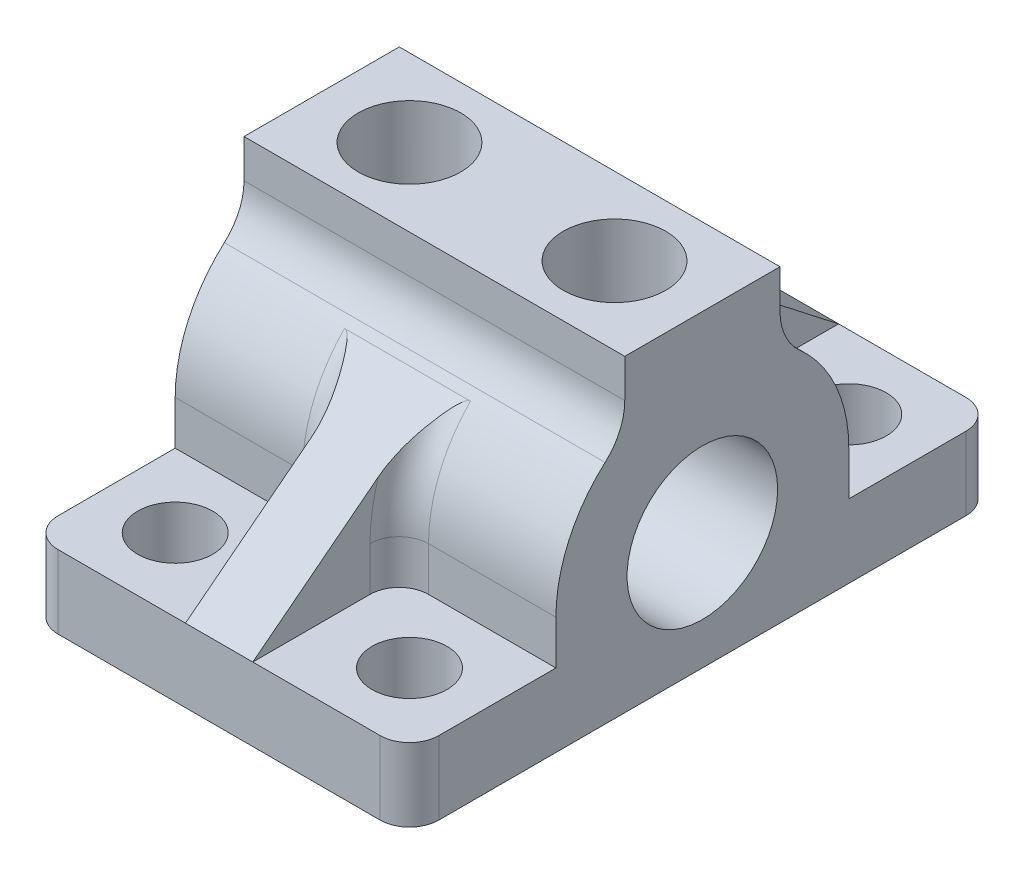
SolidWorks part; units mm, degrees
material "PLA2"
ref_plane "Front Plane" through (0, 0, 0) normal (0, 0, 1) x (1, 0, 0)
ref_plane "Top Plane" through (0, 0, 0) normal (0, 1, 0) x (1, 0, 0)
ref_plane "Right Plane" through (0, 0, 0) normal (1, 0, 0) x (0, 0, -1)
sketch "Sketch1" plane through (0, 0, 0) normal (1, 0, 0) x (0, 0, -1)
  line L0 (0, 0) -> (27506.0917, 0) construction
  line L1 (0.3138, 24.13) -> (27506.4055, 24.13) construction
  line L2 (0, 29.21) -> (0, 0) construction
  line L3 (12.7, 24.13) -> (-12.7, 24.13)
  line L4 (-12.7, 24.13) -> (-12.7, 27.305)
  line L5 (-12.7, 27.305) -> (-6.35, 27.305)
  line L6 (-6.35, 27.305) -> (-6.35, 29.21)
  line L7 (0, 29.21) -> (0, 35.56) construction
  line L8 (6.35, 27.305) -> (6.35, 29.21)
  line L9 (12.7, 27.305) -> (6.35, 27.305)
  line L10 (12.7, 24.13) -> (12.7, 27.305)
  circle A0 centre (0, 29.21) radius 3.2639
  arc A1 (6.35, 29.21) -> (-6.35, 29.21) centre (0, 29.21) ccw
  point P19 (0, 24.13)
  dimension "D2" = 6.5278
  dimension "D4" = 12.7
  dimension "D7" = 3.0861
  dimension "D1" = 24.13
  dimension "D3" = 29.21
  dimension "D5" = 3.175
  dimension "D6" = 6.35
extrude "Boss-Extrude1" add sketch "Sketch1" along normal mid plane 16.51
sketch "Sketch2" plane through (0, 0, 0) normal (1, 0, 0) x (0, 0, -1)
  line L0 (0, 32.4739) -> (0, 25.9461) construction
  line L1 (-4.5348, 33.655) -> (-12.7, 27.305)
  line L2 (-6.35, 27.305) -> (-12.7, 27.305) construction
  line L3 (-12.7, 27.305) -> (-4.5348, 27.305)
  line L4 (-4.5348, 27.305) -> (-4.5348, 33.655)
  line L5 (4.5348, 27.305) -> (4.5348, 33.655)
  line L6 (12.7, 27.305) -> (4.5348, 27.305)
  line L7 (4.5348, 33.655) -> (12.7, 27.305)
  circle A0 centre (0, 29.21) radius 3.2639 construction
  arc A1 (6.35, 29.21) -> (-6.35, 29.21) centre (0, 29.21) ccw construction
  dimension "D1" = 6.35
extrude "Boss-Extrude2" add sketch "Sketch2" along normal mid plane 2.921
sketch "Sketch3" plane through (0, 27.305, 0) normal (0, 1, 0) x (1, 0, 0)
  line L0 (-8.255, 0) -> (8.255, 0) construction
  line L1 (-8.255, 6.35) -> (-8.255, -6.35) construction
  line L2 (8.255, -6.35) -> (8.255, 6.35) construction
  line L3 (0, 12.7) -> (0, -12.7) construction
  line L4 (1.4605, 12.7) -> (-1.4605, 12.7) construction
  line L5 (1.4605, -12.7) -> (-1.4605, -12.7) construction
  circle A0 centre (-5.08, 9.525) radius 1.6256
  circle A1 centre (5.08, 9.525) radius 1.6256
  circle A2 centre (5.08, -9.525) radius 1.6256
  circle A3 centre (-5.08, -9.525) radius 1.6256
  dimension "D1" = 3.2512
  dimension "D2" = 10.16
  dimension "D3" = 19.05
extrude "Cut-Extrude1" cut sketch "Sketch3" against normal through all
sketch "Sketch4" plane through (8.255, 0, 0) normal (1, 0, 0) x (0, 0, -1)
  line L0 (3.3655, 34.5948) -> (-3.3655, 34.5948)
  arc A0 (6.35, 29.21) -> (-6.35, 29.21) centre (0, 29.21) ccw construction
  arc A1 (3.3655, 34.5948) -> (-3.3655, 34.5948) centre (0, 29.21) ccw
  dimension "D1" = 6.731
extrude "Cut-Extrude2" cut sketch "Sketch4" against normal through all
sketch "Sketch6" plane through (0, 34.5948, 0) normal (0, 1, 0) x (1, 0, 0)
  line L4 (8.255, -3.3655) -> (8.255, 3.3655)
  line L5 (8.255, 3.3655) -> (-8.255, 3.3655)
  line L6 (-8.255, 3.3655) -> (-8.255, -3.3655)
  line L7 (-8.255, -3.3655) -> (8.255, -3.3655)
  line L8 (8.255, -3.3655) -> (8.255, 3.3655)
  line L9 (8.255, 3.3655) -> (-8.255, 3.3655)
  line L10 (-8.255, 3.3655) -> (-8.255, -3.3655)
  line L11 (-8.255, -3.3655) -> (8.255, -3.3655)
  dimension "D1" = 0
extrude "Boss-Extrude3" add sketch "Sketch6" along normal blind 2.921
sketch "Sketch5" plane through (0, 37.5158, 0) normal (0, 1, 0) x (1, 0, 0)
  line L0 (0, 12.7) -> (0, -12.7) construction
  line L1 (1.4605, 12.7) -> (-1.4605, 12.7) construction
  line L2 (1.4605, -12.7) -> (-1.4605, -12.7) construction
  line L3 (-8.255, 0) -> (8.255, 0) construction
  line L6 (-8.255, 3.3655) -> (-8.255, -3.3655) construction
  line L7 (8.255, -3.3655) -> (8.255, 3.3655) construction
  circle A0 centre (-4.445, 0) radius 2.2225
  circle A1 centre (4.445, 0) radius 2.2225
  dimension "D1" = 4.445
  dimension "D2" = 8.89
extrude "Cut-Extrude3" cut sketch "Sketch5" against normal blind 6.35
fillet "Fillet1" radius 1.27 12 edges at (-1.4605, 31.6107, 5.8787) (1.4605, 31.6107, 5.8787) (-1.4605, 31.6107, -5.8787) (1.4605, 31.6107, -5.8787) (-1.4605, 28.2575, 6.35) (1.4605, 28.2575, 6.35) (-1.4605, 28.2575, -6.35) (1.4605, 28.2575, -6.35) (-8.255, 25.7175, -12.7) (8.255, 25.7175, -12.7) (-8.255, 25.7175, 12.7) (8.255, 25.7175, 12.7)
fillet "Fillet2" radius 2.54 2 edges at (0, 34.5948, -3.3655) (0, 34.5948, 3.3655)
